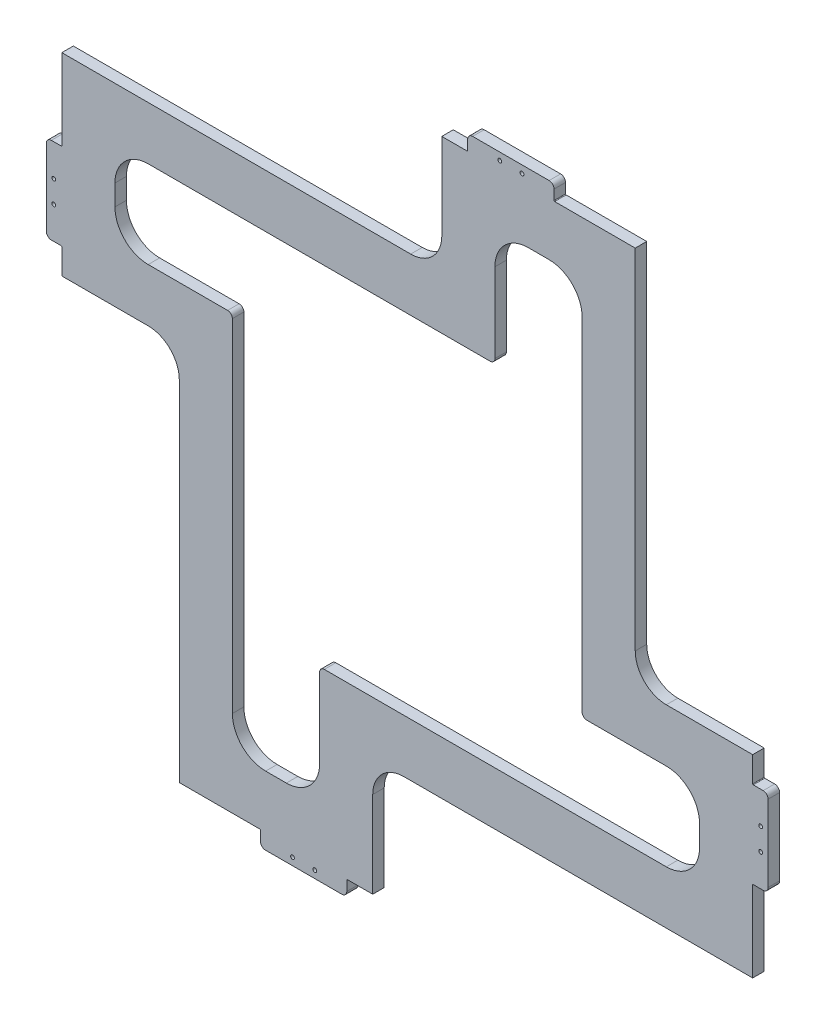
SolidWorks part; units mm, degrees
ref_plane "front" through (0, 0, 0) normal (0, 0, 1) x (1, 0, 0)
ref_plane "top" through (0, 0, 0) normal (0, 1, 0) x (1, 0, 0)
ref_plane "right" through (0, 0, 0) normal (1, 0, 0) x (0, 0, -1)
ref_axis "Axis1" through (0, 0, -69.7337) along (0, 0, 1)
sketch "Sketch1" plane through (0, 0, 0) normal (0, 0, 1) x (1, 0, 0)
  line L0 (-35.5092, 35.5092) -> (35.5092, 35.5092)
  line L1 (35.5092, 35.5092) -> (35.5092, -35.5092)
  line L2 (35.5092, -35.5092) -> (-35.5092, -35.5092)
  line L3 (-35.5092, -35.5092) -> (-35.5092, 35.5092)
  line L4 (-35.5092, 0) -> (-405.872, 0) construction
  line L5 (-405.872, 0) -> (0, 71.5662)
  line L6 (-405.872, 0) -> (0, 35.5092)
  dimension "D1" = 10
  dimension "D2" = 5
  dimension "D3" = 405.872
  dimension "D4" = 412.1332
  dimension "A" = 71.0184
sketch "Sketch2" plane through (0, 0, 0) normal (0, 0, 1) x (1, 0, 0)
  line L0 (-28.4074, 35.5092) -> (17.0444, 35.5092)
  line L1 (-35.5092, 35.5092) -> (35.5092, 35.5092) construction
  line L2 (18.4648, 36.9296) -> (18.4648, 53.2638)
  line L3 (35.5092, 53.2638) -> (35.5092, 14.2037)
  line L4 (35.5092, 14.2037) -> (46.8721, 14.2037)
  line L5 (46.8721, 14.2037) -> (46.8721, 71.0184)
  line L6 (12.3012, 71.0184) -> (7.1018, 71.0184)
  line L7 (7.1018, 53.2638) -> (18.4648, 53.2638) construction
  line L8 (7.1018, 71.0184) -> (7.1018, 53.2638)
  line L10 (46.8721, 71.0184) -> (30.3098, 71.0184)
  line L11 (30.1828, 71.1454) -> (30.1828, 73.1774)
  line L12 (29.1668, 74.1934) -> (13.4442, 74.1934)
  line L13 (12.4282, 73.1774) -> (12.4282, 71.1454)
  line L14 (0.7102, 46.8721) -> (-28.4074, 46.8721)
  line L15 (-28.4074, 46.8721) -> (-28.4074, 35.5092)
  line L16 (35.5092, 35.5092) -> (35.5092, -35.5092) construction
  line L18 (24.8564, 59.6555) -> (29.1175, 59.6555)
  arc A0 (7.1018, 53.2638) -> (0.7102, 46.8721) centre (0.7102, 53.2638) cw
  arc A1 (13.4442, 74.1934) -> (12.4282, 73.1774) centre (13.4442, 73.1774) ccw
  arc A2 (30.1828, 73.1774) -> (29.1668, 74.1934) centre (29.1668, 73.1774) ccw
  arc A3 (12.4282, 71.1454) -> (12.3012, 71.0184) centre (12.3012, 71.1454) cw
  circle A4 centre (19.0195, 72.6694) radius 0.3937
  arc A5 (30.3098, 71.0184) -> (30.1828, 71.1454) centre (30.3098, 71.1454) cw
  circle A6 centre (23.5915, 72.6694) radius 0.3937
  arc A9 (29.1175, 59.6555) -> (35.5092, 53.2638) centre (29.1175, 53.2638) cw
  arc A10 (18.4648, 53.2638) -> (24.8564, 59.6555) centre (24.8564, 53.2638) cw
  arc A11 (17.0444, 35.5092) -> (18.4648, 36.9296) centre (17.0444, 36.9296) ccw
  point P16 (21.3055, 74.1934)
  dimension "D9" = 1.4204
  dimension "D6" = 0.127
  dimension "D2" = 35.5092
  dimension "D5" = 17.7546
  dimension "D8" = 11.3629
  dimension "D10" = 11.3629
  dimension "D12" = 28.4074
  dimension "D13" = 14.2037
  dimension "D4" = 7.1018
  dimension "D15" = 39.7703
  dimension "D11" = 21.3055
  dimension "D16" = 2.286
  dimension "D17" = 2.286
extrude "Extrude1" add sketch "Sketch2" against normal mid plane 2.3622
pattern_circular "CirPattern1" count 4 over 360 about axis through (0, 0, -69.7337) along (0, 0, 1) of "Extrude1"
sketch "Sketch3" plane through (0, 0, 1.1811) normal (0, 0, 1) x (1, 0, 0)
  line L168 (29.1175, 60.1) -> (24.8564, 60.1)
  line L169 (18.0203, 53.2638) -> (18.0203, 36.9296)
  line L170 (35.9537, -17.0444) -> (35.9537, 53.2638)
  line L171 (53.2638, -18.0203) -> (36.9296, -18.0203)
  line L172 (60.1, -29.1175) -> (60.1, -24.8564)
  line L173 (-17.0444, -35.9537) -> (53.2638, -35.9537)
  line L174 (-18.0203, -53.2638) -> (-18.0203, -36.9296)
  line L175 (-29.1175, -60.1) -> (-24.8564, -60.1)
  line L176 (-35.9537, 17.0444) -> (-35.9537, -53.2638)
  line L177 (-53.2638, 18.0203) -> (-36.9296, 18.0203)
  line L178 (-60.1, 29.1175) -> (-60.1, 24.8564)
  line L179 (17.0444, 35.9537) -> (-53.2638, 35.9537)
  line L180 (29.1175, 60.1) -> (24.8564, 60.1)
  line L181 (18.0203, 53.2638) -> (18.0203, 36.9296)
  line L182 (35.9537, -17.0444) -> (35.9537, 53.2638)
  line L183 (53.2638, -18.0203) -> (36.9296, -18.0203)
  line L184 (60.1, -29.1175) -> (60.1, -24.8564)
  line L185 (-17.0444, -35.9537) -> (53.2638, -35.9537)
  line L186 (-18.0203, -53.2638) -> (-18.0203, -36.9296)
  line L187 (-29.1175, -60.1) -> (-24.8564, -60.1)
  line L188 (-35.9537, 17.0444) -> (-35.9537, -53.2638)
  line L189 (-53.2638, 18.0203) -> (-36.9296, 18.0203)
  line L190 (-60.1, 29.1175) -> (-60.1, 24.8564)
  line L191 (17.0444, 35.9537) -> (-53.2638, 35.9537)
  arc A156 (35.9537, 53.2638) -> (29.1175, 60.1) centre (29.1175, 53.2638) ccw
  arc A157 (24.8564, 60.1) -> (18.0203, 53.2638) centre (24.8564, 53.2638) ccw
  arc A158 (17.0444, 35.9537) -> (18.0203, 36.9296) centre (17.0444, 36.9296) ccw
  arc A159 (35.9537, -17.0444) -> (36.9296, -18.0203) centre (36.9296, -17.0444) ccw
  arc A160 (60.1, -24.8564) -> (53.2638, -18.0203) centre (53.2638, -24.8564) ccw
  arc A161 (53.2638, -35.9537) -> (60.1, -29.1175) centre (53.2638, -29.1175) ccw
  arc A162 (-17.0444, -35.9537) -> (-18.0203, -36.9296) centre (-17.0444, -36.9296) ccw
  arc A163 (-24.8564, -60.1) -> (-18.0203, -53.2638) centre (-24.8564, -53.2638) ccw
  arc A164 (-35.9537, -53.2638) -> (-29.1175, -60.1) centre (-29.1175, -53.2638) ccw
  arc A165 (-35.9537, 17.0444) -> (-36.9296, 18.0203) centre (-36.9296, 17.0444) ccw
  arc A166 (-60.1, 24.8564) -> (-53.2638, 18.0203) centre (-53.2638, 24.8564) ccw
  arc A167 (-53.2638, 35.9537) -> (-60.1, 29.1175) centre (-53.2638, 29.1175) ccw
  arc A168 (35.9537, 53.2638) -> (29.1175, 60.1) centre (29.1175, 53.2638) ccw
  arc A169 (24.8564, 60.1) -> (18.0203, 53.2638) centre (24.8564, 53.2638) ccw
  arc A170 (17.0444, 35.9537) -> (18.0203, 36.9296) centre (17.0444, 36.9296) ccw
  arc A171 (35.9537, -17.0444) -> (36.9296, -18.0203) centre (36.9296, -17.0444) ccw
  arc A172 (60.1, -24.8564) -> (53.2638, -18.0203) centre (53.2638, -24.8564) ccw
  arc A173 (53.2638, -35.9537) -> (60.1, -29.1175) centre (53.2638, -29.1175) ccw
  arc A174 (-17.0444, -35.9537) -> (-18.0203, -36.9296) centre (-17.0444, -36.9296) ccw
  arc A175 (-24.8564, -60.1) -> (-18.0203, -53.2638) centre (-24.8564, -53.2638) ccw
  arc A176 (-35.9537, -53.2638) -> (-29.1175, -60.1) centre (-29.1175, -53.2638) ccw
  arc A177 (-35.9537, 17.0444) -> (-36.9296, 18.0203) centre (-36.9296, 17.0444) ccw
  arc A178 (-60.1, 24.8564) -> (-53.2638, 18.0203) centre (-53.2638, 24.8564) ccw
  arc A179 (-53.2638, 35.9537) -> (-60.1, 29.1175) centre (-53.2638, 29.1175) ccw
  dimension "D1" = 0.4445
extrude "Cut-Extrude1" cut sketch "Sketch3" against normal blind 2.54
sketch "Sketch4" plane through (0, 0, 1.1811) normal (0, 0, 1) x (1, 0, 0)
  line L0 (17.0444, 35.9537) -> (-53.2638, 35.9537) construction
  line L1 (-35.9537, -35.9537) -> (35.9537, -35.9537)
  line L2 (-35.9537, -35.9537) -> (-35.9537, 35.9537)
  line L3 (-35.9537, 35.9537) -> (35.9537, 35.9537)
  line L4 (35.9537, -35.9537) -> (35.9537, 35.9537)
  line L5 (-35.9537, 17.0444) -> (-35.9537, -53.2638) construction
  line L6 (-17.0444, -35.9537) -> (53.2638, -35.9537) construction
  line L7 (35.9537, -17.0444) -> (35.9537, 53.2638) construction
sketch "Sketch5" plane through (0, 0, 1.1811) normal (0, 0, 1) x (1, 0, 0)
  line L0 (-17.0444, -35.9537) -> (53.2638, -35.9537) construction
  line L1 (-18.0203, -53.2638) -> (-18.0203, -36.9296) construction
  line L2 (17.0444, 35.9537) -> (-53.2638, 35.9537) construction
  line L3 (18.0203, 53.2638) -> (18.0203, 36.9296) construction
  line L4 (-35.9537, 35.9537) -> (35.9537, 35.9537) construction
  line L5 (35.9537, -35.9537) -> (35.9537, 35.9537) construction
  line L6 (-35.9537, -35.9537) -> (35.9537, -35.9537) construction
  line L7 (-35.9537, -35.9537) -> (-35.9537, 35.9537) construction
  circle A0 centre (53.7337, -26.9875) radius 2.0193
  circle A1 centre (-26.9865, -53.7337) radius 2.0193
  circle A2 centre (-53.7337, 26.9875) radius 2.0193
  circle A3 centre (26.9865, 53.7337) radius 2.0193
  dimension "D3" = 8.9662
  dimension "D5" = 17.78
  dimension "D7" = 17.78
  dimension "D9" = 4.0386
  dimension "D1" = 8.9662
  dimension "D2" = 8.9662
  dimension "D4" = 8.9662
  dimension "D6" = 17.78
  dimension "D8" = 17.78
sketch "Sketch6" plane through (0, 0, 1.1811) normal (0, 0, 1) x (1, 0, 0)
  line L0 (-7.1018, -71.0184) -> (-46.8721, -71.0184)
sketch "Sketch7" plane through (0, 0, 1.1811) normal (0, 0, 1) x (1, 0, 0)
  line L0 (71.0184, -7.1018) -> (71.0184, -46.8721)
  line L1 (71.0184, -12.3012) -> (71.0184, -7.1018) construction
  line L2 (71.0184, -7.1018) -> (53.2638, -7.1018) construction
sketch "Sketch8" plane through (0, 0, 1.1811) normal (0, 0, 1) x (1, 0, 0)
  line L0 (46.8721, 71.0184) -> (7.1018, 71.0184)
sketch "Sketch9" plane through (0, 0, 1.1811) normal (0, 0, 1) x (1, 0, 0)
  line L0 (-71.0184, 7.1018) -> (-71.0184, 46.8721)
equation "\"D2@Sketch2\" = .5 * \"A\""
equation "\"D13@Sketch2\" = .2 * \"A\""
equation "\"D8@Sketch2\" = .16 * \"A\""
equation "\"D10@Sketch2\" = .16 * \"A\""
equation "\"D5@Sketch2\" = .25 * \"A\""
equation "\"D12@Sketch2\" = .4 * \"A\""
equation "\"D4@Sketch2\"=.1*\"A\""
equation "\"D9@Sketch2\"=.02*\"A\""
equation "\"D11@Sketch2\"=.3*\"A\""
